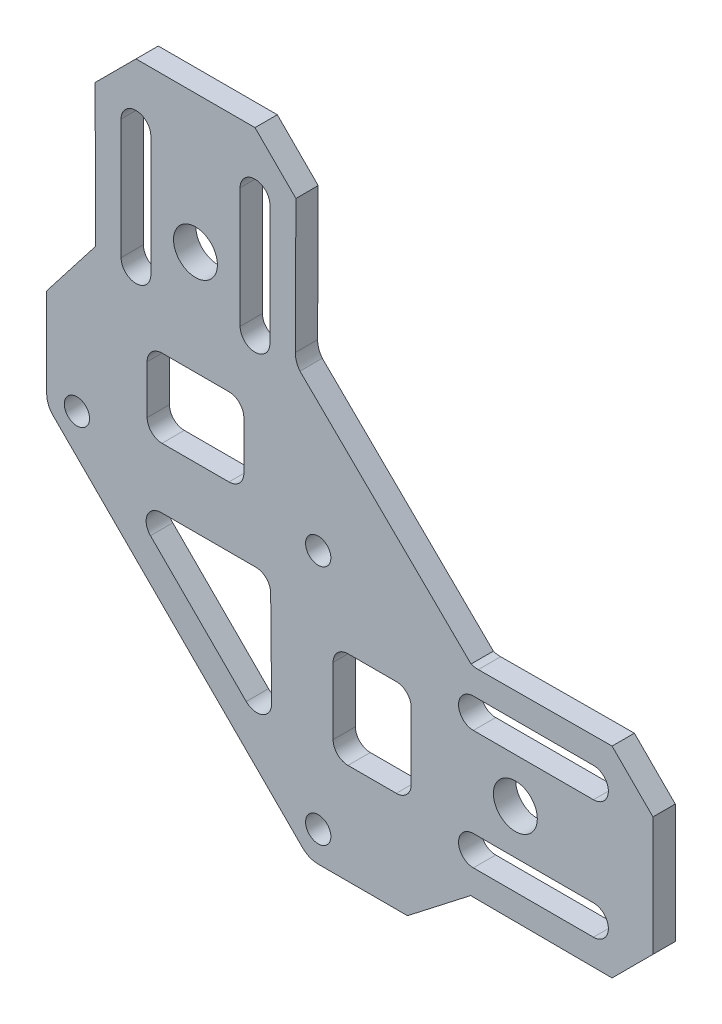
SolidWorks part; units mm, degrees
material "Thornel Mat VMA"
ref_plane "前视基准面" through (0, 0, 0) normal (0, 0, 1) x (1, 0, 0)
ref_plane "上视基准面" through (0, 0, 0) normal (0, 1, 0) x (1, 0, 0)
ref_plane "右视基准面" through (0, 0, 0) normal (1, 0, 0) x (0, 0, -1)
sketch "草图1" plane through (0, 0, 0) normal (0, 0, 1) x (1, 0, 0)
  line L0 (20, 48) -> (20, 0) construction
  line L1 (0, 0) -> (40, 0)
  line L2 (0, 0) -> (0, 48)
  line L3 (0, 48) -> (40, 48)
  line L4 (40, 0) -> (40, 48)
  dimension "D1" = 48
  dimension "D2" = 40
extrude "凸台-拉伸1" add sketch "草图1" along normal blind 3
chamfer "倒角1" distance 12 angle 45 2 edges at (40, 48, 1.5) (0, 48, 1.5)
sketch "草图2" plane through (0, 0, 0) normal (0, 0, -1) x (-1, 0, 0)
  line L0 (-6.6768, 4.4738) -> (-6.5, 42.5)
  line L1 (0, 36) -> (-12, 48) construction
  line L2 (-6.5, 42.5) -> (0, 36)
  line L3 (0, 36) -> (0, 0)
  line L4 (0, 36) -> (0, 0) construction
  line L5 (0, 0) -> (-1.3496, 1.7221)
  line L6 (-20, 48) -> (-20, 0) construction
  line L7 (-28, 48) -> (-12, 48) construction
  line L8 (0, 0) -> (-40, 0) construction
  line L9 (-33.5, 42.5) -> (-40, 36)
  line L10 (-40, 36) -> (-40, 0)
  line L11 (-40, 0) -> (-38.6504, 1.7221)
  line L12 (-33.3232, 4.4738) -> (-33.5, 42.5)
  line L13 (-24.5, 7) -> (-24.5, 13.5) construction
  line L14 (-24.5, 13.5) -> (-15.5, 13.5) construction
  line L15 (-15.5, 13.5) -> (-15.5, 7) construction
  line L16 (-15.5, 7) -> (-24.5, 7) construction
  line L17 (-13.5, 5) -> (-26.5, 5)
  line L18 (-26.5, 5) -> (-26.5, 15.5)
  line L19 (-26.5, 15.5) -> (-13.5, 15.5)
  line L20 (-13.5, 15.5) -> (-13.5, 5)
  arc A0 (-1.3496, 1.7221) -> (-6.6768, 4.4738) centre (-4.0638, 3) ccw
  arc A1 (-38.6504, 1.7221) -> (-33.3232, 4.4738) centre (-35.9362, 3) cw
  circle A2 centre (-20, 29.5) radius 2.95
  dimension "D1" = 2
  dimension "D2" = 5.9
extrude "切除-拉伸1" cut sketch "草图2" against normal blind 10
sketch "草图6" plane through (0, 0, 3) normal (0, 0, 1) x (1, 0, 0)
  line L0 (0, 0) -> (0, 15)
  line L1 (0, 15) -> (6.5884, 23.4869)
  line L2 (6.5, 42.5) -> (6.6768, 4.4738) construction
  line L3 (6.5884, 23.4869) -> (6.6768, 4.4738)
  line L4 (6.6768, 4.4738) -> (1.4507, 4.4738)
  line L5 (1.4507, 4.4738) -> (1.4507, 0)
  line L6 (0, 0) -> (40, 0) construction
  line L7 (20, 48) -> (20, 0) construction
  line L8 (28, 48) -> (12, 48) construction
  line L9 (40, 15) -> (33.4116, 23.4869)
  line L10 (33.4116, 23.4869) -> (33.3232, 4.4738)
  line L11 (33.3232, 4.4738) -> (38.5493, 4.4738)
  line L12 (38.5493, 4.4738) -> (38.5493, 0)
  line L13 (40, 0) -> (40, 15)
  line L14 (0, 0) -> (1.4507, 0)
  line L15 (38.5493, 0) -> (40, 0)
  arc A0 (6.6768, 4.4738) -> (1.3496, 1.7221) centre (4.0638, 3) ccw construction
  dimension "D1" = 15
extrude "凸台-拉伸2" add sketch "草图6" against normal blind 3
fillet "圆角1" radius 2 4 edges at (26.5, 5, 1.5) (13.5, 5, 1.5) (26.5, 15.5, 1.5) (13.5, 15.5, 1.5)
sketch "草图7" plane through (0, 0, 3) normal (0, 0, 1) x (1, 0, 0)
  line L0 (20, 48) -> (20, 0) construction
  line L1 (28, 48) -> (12, 48) construction
  line L2 (0, 0) -> (40, 0) construction
  line L3 (12, 40) -> (12, 23.8573) construction
  line L4 (14, 40) -> (14, 23.8573)
  line L5 (10, 40) -> (10, 23.8573)
  line L6 (28, 40) -> (28, 23.8573) construction
  line L7 (26, 40) -> (26, 23.8573)
  line L8 (30, 40) -> (30, 23.8573)
  arc A0 (14, 40) -> (10, 40) centre (12, 40) ccw
  arc A1 (10, 23.8573) -> (14, 23.8573) centre (12, 23.8573) ccw
  arc A2 (26, 40) -> (30, 40) centre (28, 40) cw
  arc A3 (30, 23.8573) -> (26, 23.8573) centre (28, 23.8573) cw
  point P8 (12, 31.9287)
  point P15 (28, 31.9287)
  dimension "D1" = 8
  dimension "D2" = 4
  dimension "D3" = 8
extrude "切除-拉伸3" cut sketch "草图7" against normal blind 3
sketch "草图10" plane through (0, 0, 0) normal (0, 0, -1) x (-1, 0, 0)
  circle A0 centre (-4.0638, 3) radius 1.7
  circle A1 centre (-36.5, 3) radius 1.7
  dimension "D1" = 3.4
  dimension "D2" = 3.4
extrude "切除-拉伸4" cut sketch "草图10" against normal blind 3
sketch "草图12" plane through (0, 0, 3) normal (0, 0, 1) x (1, 0, 0)
  line L0 (40, 0) -> (0, 0) construction
  line L1 (36.5, 3) -> (23.8762, -9.6238) construction
  line L2 (33.5, -33.5) -> (33.5, 6.5)
  line L3 (33.5, 6.5) -> (48.5, 6.5)
  line L4 (48.5, 6.5) -> (56.9869, -0.0884)
  line L5 (56.9869, -0.0884) -> (76, 0)
  line L6 (76, 0) -> (81.5, -5.5)
  line L7 (81.5, -5.5) -> (81.5, -21.5)
  line L8 (81.5, -21.5) -> (76, -27)
  line L9 (76, -27) -> (56.9869, -26.9116)
  line L10 (56.9869, -26.9116) -> (48.5, -33.5)
  line L11 (48.5, -33.5) -> (33.5, -33.5)
  line L12 (0, 0) -> (40, 0)
  line L13 (40, 0) -> (40, 15)
  line L14 (40, 15) -> (33.4116, 23.4869)
  line L15 (33.4116, 23.4869) -> (33.5, 42.5)
  line L16 (33.5, 42.5) -> (28, 48)
  line L17 (28, 48) -> (12, 48)
  line L18 (12, 48) -> (6.5, 42.5)
  line L19 (6.5, 42.5) -> (6.5884, 23.4869)
  line L20 (6.5884, 23.4869) -> (0, 15)
  line L21 (0, 15) -> (0, 0)
  line L22 (0, 0) -> (40, 0)
  line L23 (40, 0) -> (40, 15)
  line L24 (40, 15) -> (33.4116, 23.4869)
  line L25 (33.4116, 23.4869) -> (33.5, 42.5)
  line L26 (33.5, 42.5) -> (28, 48)
  line L27 (28, 48) -> (12, 48)
  line L28 (12, 48) -> (6.5, 42.5)
  line L29 (6.5, 42.5) -> (6.5884, 23.4869)
  line L30 (6.5884, 23.4869) -> (0, 15)
  line L31 (0, 15) -> (0, 0)
  line L32 (10, 40) -> (10, 23.8573) construction
  line L33 (14, 23.8573) -> (14, 40) construction
  line L34 (10, 40) -> (10, 23.8573)
  line L35 (14, 23.8573) -> (14, 40)
  line L36 (10, 40) -> (10, 23.8573)
  line L37 (14, 23.8573) -> (14, 40)
  line L38 (26, 40) -> (26, 23.8573)
  line L39 (30, 23.8573) -> (30, 40)
  line L40 (26, 40) -> (26, 23.8573)
  line L41 (30, 23.8573) -> (30, 40)
  line L42 (26, 40) -> (26, 23.8573) construction
  line L43 (30, 23.8573) -> (30, 40) construction
  line L44 (26.5, 7) -> (26.5, 13.5)
  line L45 (15.5, 5) -> (24.5, 5)
  line L46 (13.5, 13.5) -> (13.5, 7)
  line L47 (24.5, 15.5) -> (15.5, 15.5)
  line L48 (26.5, 7) -> (26.5, 13.5)
  line L49 (15.5, 5) -> (24.5, 5)
  line L50 (13.5, 13.5) -> (13.5, 7)
  line L51 (24.5, 15.5) -> (15.5, 15.5)
  line L52 (10, 40) -> (10, 23.8573)
  line L53 (14, 23.8573) -> (14, 40)
  line L54 (26, 40) -> (26, 23.8573)
  line L55 (30, 23.8573) -> (30, 40)
  line L56 (57.3573, -3.5) -> (73.5, -3.5)
  line L57 (73.5, -7.5) -> (57.3573, -7.5)
  line L58 (73.5, -23.5) -> (57.3573, -23.5)
  line L59 (57.3573, -19.5) -> (73.5, -19.5)
  line L60 (38.5, -18) -> (38.5, -9)
  line L61 (40.5, -7) -> (47, -7)
  line L62 (49, -9) -> (49, -18)
  line L63 (47, -20) -> (40.5, -20)
  arc A0 (14, 40) -> (10, 40) centre (12, 40) ccw construction
  circle A1 centre (20, 29.5) radius 2.95
  circle A2 centre (20, 29.5) radius 2.95
  circle A3 centre (4.0638, 3) radius 1.7
  circle A4 centre (4.0638, 3) radius 1.7
  arc A5 (26, 23.8573) -> (30, 23.8573) centre (28, 23.8573) ccw construction
  arc A6 (14, 40) -> (10, 40) centre (12, 40) ccw
  arc A7 (10, 23.8573) -> (14, 23.8573) centre (12, 23.8573) ccw
  arc A8 (14, 40) -> (10, 40) centre (12, 40) ccw
  arc A9 (10, 23.8573) -> (14, 23.8573) centre (12, 23.8573) ccw
  arc A10 (30, 40) -> (26, 40) centre (28, 40) ccw
  arc A11 (26, 23.8573) -> (30, 23.8573) centre (28, 23.8573) ccw
  arc A12 (30, 40) -> (26, 40) centre (28, 40) ccw
  arc A13 (26, 23.8573) -> (30, 23.8573) centre (28, 23.8573) ccw
  arc A14 (13.5, 7) -> (15.5, 5) centre (15.5, 7) ccw construction
  arc A15 (14, 40) -> (10, 40) centre (12, 40) ccw
  arc A16 (24.5, 5) -> (26.5, 7) centre (24.5, 7) ccw
  arc A17 (13.5, 7) -> (15.5, 5) centre (15.5, 7) ccw
  arc A18 (15.5, 15.5) -> (13.5, 13.5) centre (15.5, 13.5) ccw
  arc A19 (26.5, 13.5) -> (24.5, 15.5) centre (24.5, 13.5) ccw
  arc A20 (24.5, 5) -> (26.5, 7) centre (24.5, 7) ccw
  arc A21 (13.5, 7) -> (15.5, 5) centre (15.5, 7) ccw
  arc A22 (15.5, 15.5) -> (13.5, 13.5) centre (15.5, 13.5) ccw
  arc A23 (26.5, 13.5) -> (24.5, 15.5) centre (24.5, 13.5) ccw
  arc A24 (26, 23.8573) -> (30, 23.8573) centre (28, 23.8573) ccw
  arc A25 (13.5, 7) -> (15.5, 5) centre (15.5, 7) ccw
  arc A26 (73.5, -19.5) -> (73.5, -23.5) centre (73.5, -21.5) cw
  arc A27 (73.5, -3.5) -> (73.5, -7.5) centre (73.5, -5.5) cw
  arc A28 (57.3573, -7.5) -> (57.3573, -3.5) centre (57.3573, -5.5) cw
  arc A29 (57.3573, -23.5) -> (57.3573, -19.5) centre (57.3573, -21.5) cw
  circle A30 centre (63, -13.5) radius 2.95
  arc A31 (38.5, -9) -> (40.5, -7) centre (40.5, -9) cw
  arc A32 (40.5, -20) -> (38.5, -18) centre (40.5, -18) cw
  arc A33 (47, -7) -> (49, -9) centre (47, -9) cw
  arc A34 (49, -18) -> (47, -20) centre (47, -18) cw
  circle A35 centre (36.5, -29.4362) radius 1.7
  line M41 (0, 0) -> (40, 0)
  line M42 (40, 0) -> (40, 15)
  dimension "D1" = 45
  dimension "D2" = 0
  dimension "D3" = 0
  dimension "D4" = 0
  dimension "D5" = 0
  dimension "D6" = 0
  dimension "D7" = 0
extrude "凸台-拉伸4" add sketch "草图12" against normal blind 3 contours L11 L10 L9 L8 L7 L6 L5 L4 L3 L2 L62 A34 L63 A32 L60 A31 L61 A33 A30 L57 A28 L56 A27 L58 A29 L59 A26 A35 M42 M41 region at (55.1363, -13.9906, 3)
fillet "圆角2" radius 3 3 edges at (33.5, -33.5, 1.5) (0, 0, 1.5) (33.5, 0, 1.5)
fillet "圆角3" radius 13 1 edges at (40, 6.5, 1.5)
fillet "圆角4" radius 3 2 edges at (56.9869, -0.0884, 1.5) (33.4116, 23.4869, 1.5)
sketch "草图13" plane through (0, 0, 3) normal (0, 0, 1) x (1, 0, 0)
  line L0 (34.0466, 22.6689) -> (57.0428, 0.0761)
  line L1 (57.0428, 0.0761) -> (39.4911, 6.0436)
  line L2 (39.4911, 6.0436) -> (34.0466, 22.6689)
  line L3 (0.8787, 0.8787) -> (34.3787, -32.6213)
  line L4 (0.8787, 0.8787) -> (34.0466, 0.8787)
  line L5 (34.0466, 0.8787) -> (34.3787, -32.6213)
  line L6 (10.5355, -3.1213) -> (30.2818, -22.8676)
  line L7 (30.0861, -3.1213) -> (30.2818, -22.8676)
  line L8 (10.5355, -3.1213) -> (30.0861, -3.1213)
  arc A0 (56.1689, 0.5466) -> (58.0225, -0.0836) centre (58.0085, 2.9164) ccw construction
  arc A1 (0, 3) -> (3, 0) centre (3, 3) ccw construction
  arc A2 (33.5, -30.5) -> (36.5, -33.5) centre (36.5, -30.5) ccw construction
  dimension "D1" = 4
extrude "凸台-拉伸5" add sketch "草图13" against normal blind 3
fillet "圆角5" radius 2 3 edges at (30.2818, -22.8676, 1.5) (10.5355, -3.1213, 1.5) (30.0861, -3.1213, 1.5)
